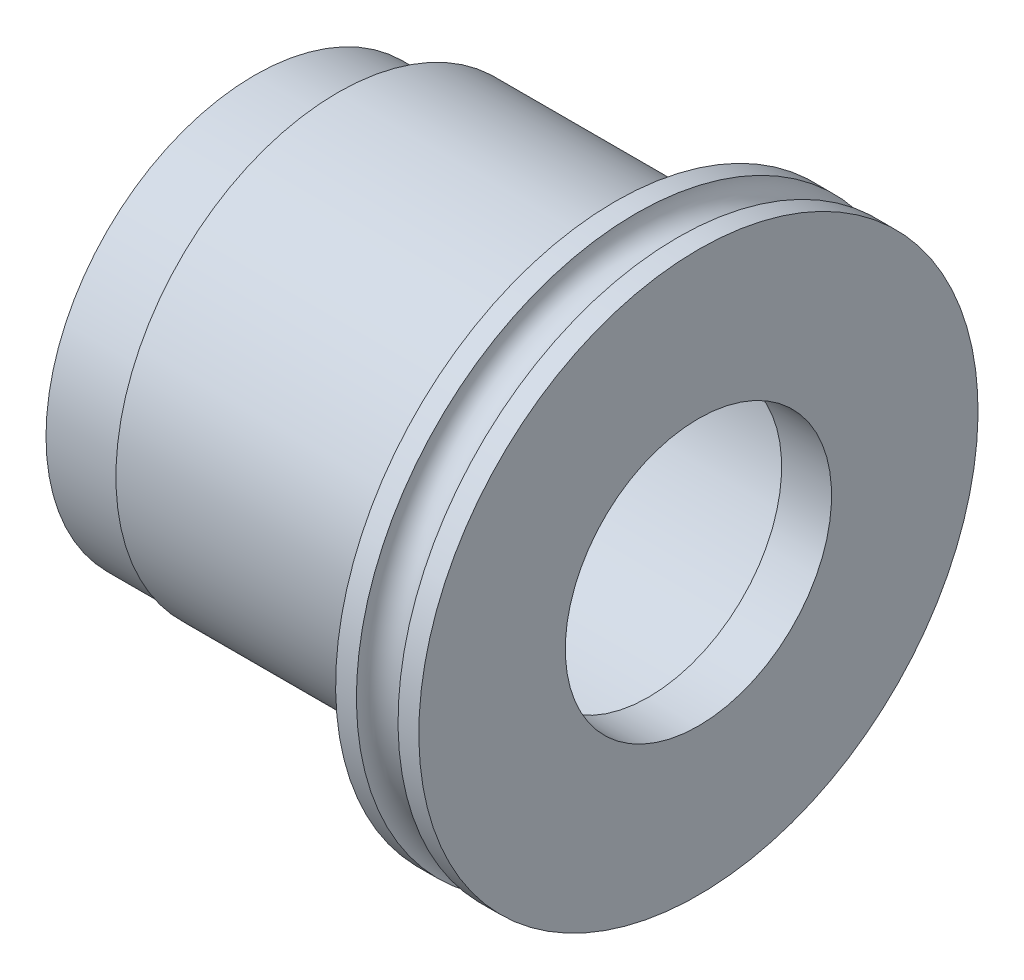
SolidWorks part; units mm, degrees
material "ABS"
ref_plane "Front Plane" through (0, 0, 0) normal (0, 0, 1) x (1, 0, 0)
ref_plane "Top Plane" through (0, 0, 0) normal (0, 1, 0) x (1, 0, 0)
ref_plane "Right Plane" through (0, 0, 0) normal (1, 0, 0) x (0, 0, -1)
sketch "Sketch1" plane through (0, 0, 0) normal (0, 0, 1) x (1, 0, 0)
  line L0 (-7.9375, 12.7) -> (-7.9375, 0)
  line L1 (7.9375, 0) -> (7.9375, 12.7)
  line L2 (7.9375, 12.7) -> (-7.9375, 12.7)
  line L3 (-7.9375, 0) -> (7.9375, 0)
  point P3 (4.8626, -0.7045)
  point P6 (0, 0)
  dimension "D1" = 12.7
  dimension "D2" = 15.875
revolve "Colar press section" add sketch "Sketch1" angle 360 about L3
sketch "Axis Referance" plane through (0, 0, 0) normal (0, 0, 1) x (1, 0, 0)
  line L0 (7.9375, -0.762) -> (-7.9375, -0.762)
  line L1 (7.9375, -12.7) -> (7.9375, 12.7) construction
  line L2 (-7.9375, 12.7) -> (-7.9375, -12.7) construction
  dimension "D1" = 0.762
ref_axis "Center of Shaft Colar" through (-34.8631, 0, 0) along (1, 0, 0)
ref_axis "Center of Rotation" through (39.065, -0.762, 0) along (-1, 0, 0)
sketch "Sketch7" plane through (0, 0, 0) normal (0, 0, 1) x (1, 0, 0)
  line L0 (39.065, -0.762) -> (-26.3455, -0.762) construction
  line L1 (12.7, -0.762) -> (7.9375, -0.762)
  line L2 (12.7, -0.762) -> (12.7, 15.24)
  line L3 (12.7, 15.24) -> (11.5094, 15.24)
  line L4 (7.9375, -0.762) -> (7.9375, 15.24)
  line L5 (7.9375, -12.7) -> (7.9375, 12.7) construction
  line L6 (7.9375, 12.7) -> (-7.9375, 12.7) construction
  line L7 (-7.9375, 12.7) -> (-7.9375, -12.7) construction
  line L8 (-12.7, -0.762) -> (-7.9375, -0.762)
  line L9 (-12.7, -0.762) -> (-12.7, -12.7)
  line L10 (-12.7, -12.7) -> (-11.5094, -12.7)
  line L11 (-7.9375, -0.762) -> (-7.9375, -12.7)
  line L12 (9.1281, 15.24) -> (7.9375, 15.24)
  line L13 (-9.1281, -12.7) -> (-7.9375, -12.7)
  line L14 (-11.5094, -12.7) -> (-9.1281, -12.7)
  arc A0 (9.1281, 15.24) -> (11.5094, 15.24) centre (10.3187, 15.24) ccw
  point P6 (-17.6273, -0.762)
  dimension "D1" = 2.54
  dimension "D2" = 4.7625
revolve "Revolve2" add sketch "Sketch7" angle 360 about axis through (39.065, -0.762, 0) along (-1, 0, 0)
sketch "Sketch8" plane through (0, 0, 0) normal (0, 0, 1) x (1, 0, 0)
  line L0 (39.065, -0.762) -> (-26.3455, -0.762) construction
  line L1 (9.8425, -0.762) -> (-12.7, -0.762)
  line L2 (9.8425, -0.762) -> (9.8425, 10.238)
  line L3 (9.8425, 10.238) -> (-12.7, 10.238)
  line L4 (-12.7, -0.762) -> (-12.7, 10.238)
  line L5 (7.9375, 15.24) -> (7.9375, -16.764) construction
  line L6 (-12.7, 11.176) -> (-12.7, -12.7) construction
  line L7 (12.7, -16.764) -> (12.7, 15.24) construction
  line L8 (9.8425, -0.762) -> (12.7, -0.762)
  line L9 (9.8425, -0.762) -> (9.8425, 6.858)
  line L10 (9.8425, 6.858) -> (12.7, 6.858)
  line L11 (12.7, -0.762) -> (12.7, 6.858)
  point P8 (12.7, 6.858)
  dimension "D1" = 11
  dimension "D2" = 1.905
  dimension "D3" = 7.62
revolve "Cut-Revolve3" cut sketch "Sketch8" angle 360 about axis through (39.065, -0.762, 0) along (-1, 0, 0) region at (-1.4288, 4.738, 0) region at (11.2713, 3.048, 0)
sketch "Sketch9" plane through (0, 0, 0) normal (0, 0, 1) x (1, 0, 0)
  line L0 (-12.7, 10.238) -> (-12.7, 11.176)
  line L1 (-12.7, 11.176) -> (-12.7, -12.7) construction
  point P2 (0, 0)
  point P6 (0, 0)
  dimension "D1" = 0.938
